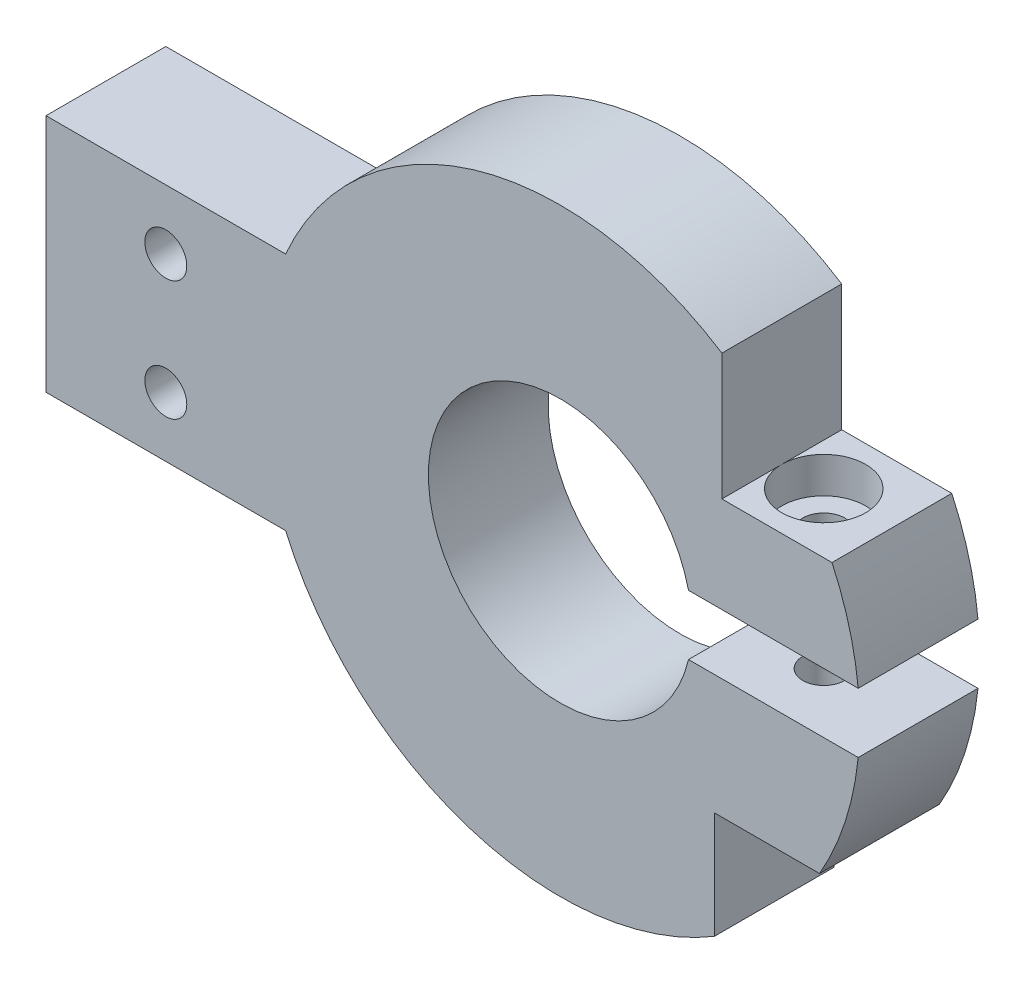
SolidWorks part; units mm, degrees
ref_plane "Front Plane" through (0, 0, 0) normal (0, 0, 1) x (1, 0, 0)
ref_plane "Top Plane" through (0, 0, 0) normal (0, 1, 0) x (1, 0, 0)
ref_plane "Right Plane" through (0, 0, 0) normal (1, 0, 0) x (0, 0, -1)
sketch "Sketch1" plane through (0, 0, 0) normal (0, 0, 1) x (1, 0, 0)
  circle A0 centre (0, 0) radius 11
  circle A1 centre (0, 0) radius 25
  dimension "D1" = 22
  dimension "D2" = 50
extrude "Boss-Extrude1" add sketch "Sketch1" along normal blind 10
sketch "Sketch2" plane through (0, 0, 10) normal (0, 0, 1) x (1, 0, 0)
  line L1 (25, 26.0035) -> (25, -24.7492) construction
  line L2 (25, 0) -> (25, 2.5)
  line L4 (0, 0) -> (0, -2.5)
  line L5 (0, -2.5) -> (25, -2.5)
  line L6 (25, 0) -> (25, -2.5)
  line L7 (25, 2.5) -> (0, 2.5)
  line L8 (0, 2.5) -> (0, 0)
  circle A0 centre (0, 0) radius 25 construction
  dimension "D1" = 2.5
  dimension "D2" = 2.5
extrude "Cut-Extrude1" cut sketch "Sketch2" against normal blind 10
sketch "Sketch5" plane through (0, -2.5, 0) normal (0, 1, 0) x (1, 0, 0)
  line L0 (10.7121, 0) -> (10.7121, -10) construction
  line L1 (10.7121, 0) -> (10.7121, -10) construction
  line L2 (24.8747, 0) -> (15.8747, 0) construction
  line L3 (24.8747, 0) -> (10.7121, 0) construction
  line L4 (17, -5) -> (13.0294, -5) construction
  circle A0 centre (17, -5) radius 1.75
  dimension "D2" = 3.5
  dimension "D1" = 9
extrude "Cut-Extrude4" cut sketch "Sketch5" against normal through all both and the other way through all
sketch "Sketch6" plane through (0, -2.5, 0) normal (0, 1, 0) x (1, 0, 0)
  line L0 (17, -5) -> (11.2324, -5) construction
  circle A1 centre (17, -5) radius 3.5
  dimension "D1" = 7
extrude "Cut-Extrude5" cut sketch "Sketch6" against normal blind 20 from offset 30
sketch "Sketch7" plane through (0, -2.5, 0) normal (0, 1, 0) x (1, 0, 0)
  line L0 (17, -5) -> (17.44, -5) construction
  line L3 (21.0415, -5) -> (19.0207, -1.5)
  line L4 (19.0207, -1.5) -> (14.9793, -1.5)
  line L5 (14.9793, -1.5) -> (12.9585, -5)
  line L6 (12.9585, -5) -> (14.9793, -8.5)
  line L7 (14.9793, -8.5) -> (19.0207, -8.5)
  line L8 (19.0207, -8.5) -> (21.0415, -5)
  circle A1 centre (17, -5) radius 3.5 construction
  dimension "D1" = 7
extrude "Cut-Extrude6" cut sketch "Sketch7" along normal blind 25 from offset 30 offset against normal yes
sketch "Sketch8" plane through (0, -7.5, 0) normal (0, -1, 0) x (1, 0, 0)
  line L0 (17, 5) -> (8.6796, 5) construction
  line L1 (12.8668, 5) -> (12.8668, -1.9178)
  line L2 (12.8668, -1.9178) -> (27.2003, -1.9178)
  line L3 (27.2003, -1.9178) -> (26.8664, 13.4403)
  line L4 (26.8664, 13.4403) -> (13.0822, 14.0127)
  line L5 (13.0822, 14.0127) -> (12.8668, 14.6173)
  line L6 (12.8668, 14.6173) -> (12.8668, 5)
extrude "Cut-Extrude8" cut sketch "Sketch8" against normal blind 15 from offset 20
sketch "Sketch9" plane through (0, 0, 0) normal (0, 0, -1) x (-1, 0, 0)
  line L2 (26.5121, 9.9977) -> (22.9139, 9.9977) construction
  line L3 (22.9139, 9.9977) -> (22.9139, -9.9977)
  line L4 (22.9139, -9.9977) -> (42.9139, -9.9977)
  line L5 (42.9139, -9.9977) -> (42.9139, 9.9977)
  line L6 (42.9139, 9.9977) -> (22.9139, 9.9977)
  line L7 (22.9139, 9.9977) -> (42.9139, -9.9977) construction
  line L8 (42.9139, 9.9977) -> (22.9139, -9.9977) construction
  line L10 (32.9139, 0) -> (42.9139, 0) construction
  arc A0 (-12.8668, -21.4347) -> (-24.8747, 2.5) centre (0, 0) ccw construction
  circle A1 centre (32.9139, 5) radius 1.75
  circle A2 centre (32.9139, -5) radius 1.75
  dimension "D2" = 3.5
  dimension "D1" = 20
extrude "Boss-Extrude2" add sketch "Sketch9" against normal blind 10
sketch "Sketch12" plane through (0, 7.5, 0) normal (0, 1, 0) x (1, 0, 0)
  line L0 (13.5, -5) -> (13.5, -13.9272)
  line L1 (13.5, -13.9272) -> (27.5495, -13.9272)
  line L2 (27.5495, -13.9272) -> (27.5495, 2.1797)
  line L3 (27.5495, 2.1797) -> (13.5, 2.1797)
  line L4 (13.5, 2.1797) -> (13.5, -5)
  circle A0 centre (17, -5) radius 3.5 construction
  circle A1 centre (17, -5) radius 3.5 construction
extrude "Cut-Extrude10" cut sketch "Sketch12" against normal blind 17 and the other way blind 1 from offset 20
sketch "Sketch13" plane through (0, 0, 0) normal (0, 0, -1) x (-1, 0, 0)
  line L0 (34.6639, 5) -> (31.1639, 5) construction
  line L1 (31.1639, -5) -> (34.6639, -5) construction
  circle A0 centre (32.9139, 5) radius 1.75 construction
  circle A1 centre (32.9139, 5) radius 3.5
  circle A2 centre (32.9139, -5) radius 1.75 construction
  circle A3 centre (32.9139, -5) radius 3.5
  dimension "D1" = 7
extrude "Cut-Extrude11" cut sketch "Sketch13" against normal blind 5
